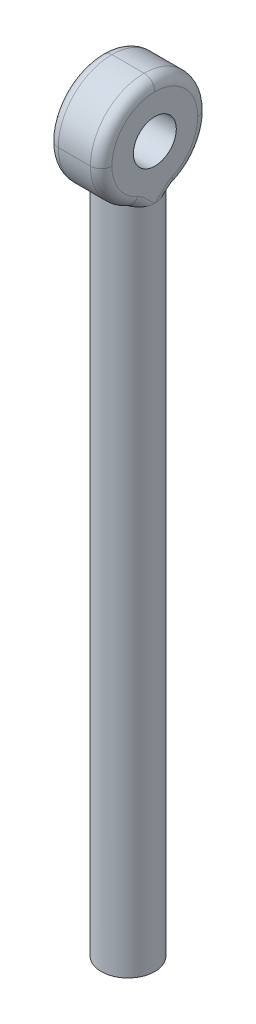
SolidWorks part; units mm, degrees
material "AISI 304"
ref_plane "Alzado" through (0, 0, 0) normal (0, 0, 1) x (1, 0, 0)
ref_plane "Planta" through (0, 0, 0) normal (0, 1, 0) x (1, 0, 0)
ref_plane "Vista lateral" through (0, 0, 0) normal (1, 0, 0) x (0, 0, -1)
sketch "Croquis1" plane through (0, 0, 0) normal (0, 1, 0) x (1, 0, 0)
  circle A0 centre (0, 0) radius 2.5
  dimension "D1" = 5
extrude "Saliente-Extruir1" add sketch "Croquis1" along normal blind 62
sketch "Croquis2" plane through (0, 62, 0) normal (0, 1, 0) x (1, 0, 0)
  line L1 (-2.5, 5) -> (2.5, 5)
  line L2 (-2.5, 5) -> (-2.5, -5)
  line L3 (-2.5, -5) -> (2.5, -5)
  line L4 (2.5, 5) -> (2.5, -5)
  line L5 (-2.5, 5) -> (2.5, -5) construction
  line L6 (-2.5, -5) -> (2.5, 5) construction
  point P0 (0, 0)
  dimension "D1" = 5
  dimension "D2" = 10
extrude "Saliente-Extruir3" add sketch "Croquis2" along normal blind 10
fillet "Redondeo1" radius 5 4 edges at (0, 62, -5) (0, 62, 5) (0, 72, -5) (0, 72, 5)
sketch "Croquis3" plane through (2.5, 0, 0) normal (1, 0, 0) x (0, 0, -1)
  line L0 (-5, 67) -> (5, 67) construction
  circle A0 centre (0, 67) radius 2
  dimension "D1" = 4
extrude "Cortar-Extruir1" cut sketch "Croquis3" against normal blind 10
fillet "Redondeo2" radius 1 8 edges at (-2.5, 63.4645, -3.5355) (-2.5, 70.5355, -3.5355) (-2.5, 70.5355, 3.5355) (-2.5, 63.4645, 3.5355) (2.5, 63.4645, 3.5355) (2.5, 63.4645, -3.5355) (2.5, 70.5355, -3.5355) (2.5, 70.5355, 3.5355)
